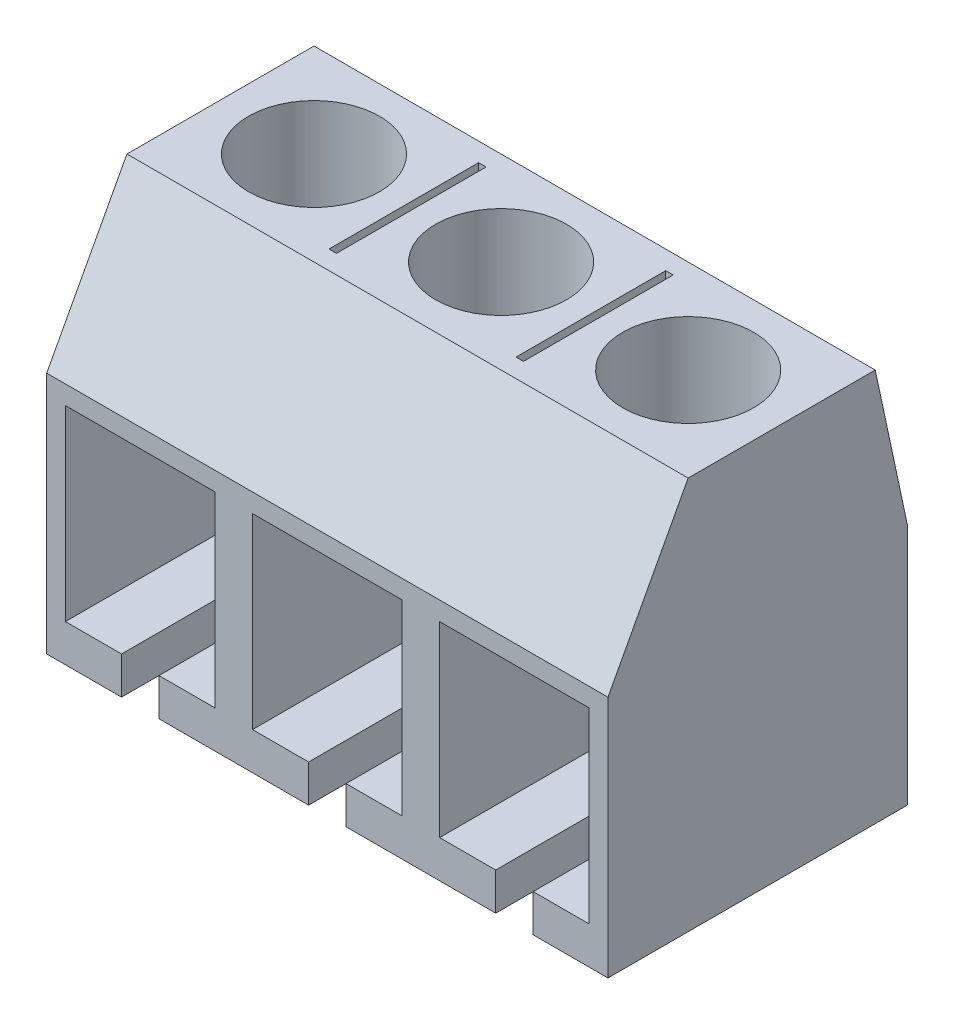
SolidWorks part; units mm, degrees
ref_plane "Ön Düzlem" through (0, 0, 0) normal (0, 0, 1) x (1, 0, 0)
ref_plane "Üst Düzlem" through (0, 0, 0) normal (0, 1, 0) x (1, 0, 0)
ref_plane "Sağ Düzlem" through (0, 0, 0) normal (1, 0, 0) x (0, 0, -1)
sketch "Çizim1" plane through (0, 0, 0) normal (1, 0, 0) x (0, 0, -1)
  line L0 (-4, 1) -> (4, 1) construction
  line L1 (-1.8562, 5) -> (3.1438, 5)
  line L2 (-4, 1) -> (-4, -5.5)
  line L3 (-4, -5.5) -> (4, -5.5)
  line L4 (4, 1) -> (4, -5.5)
  line L5 (-2.6115, 3.5908) -> (4, -5.5) construction
  line L6 (-4, -5.5) -> (3.2558, 4.4767) construction
  line L7 (-4, 1) -> (-1.8562, 5)
  line L8 (4, 1) -> (3.1438, 5)
  point P0 (0, 0)
  dimension "D1" = 10.5
  dimension "D2" = 8
  dimension "D3" = 4
  dimension "D4" = 5
extrude "Yükseklik-Ekstrüzyon1" add sketch "Çizim1" along normal blind 7.5 and the other way blind 7.5
sketch "Çizim2" plane through (0, 0, -4) normal (0, 0, -1) x (-1, 0, 0)
  line L0 (0, 1) -> (0, -5.5) construction
  line L1 (7.5, 1) -> (-7.5, 1) construction
  line L2 (7.5, -5.5) -> (-7.5, -5.5) construction
  line L3 (-0.5, -4.5) -> (-0.5, -5.5)
  line L4 (-2, 0.5) -> (2, 0.5)
  line L5 (-2, 0.5) -> (-2, -4.5)
  line L6 (-2, -4.5) -> (-0.5, -4.5)
  line L7 (2, 0.5) -> (2, -4.5)
  line L8 (-2, 0.5) -> (2, -4.5) construction
  line L9 (-2, -4.5) -> (2, 0.5) construction
  line L10 (0.5, -4.5) -> (0.5, -5.5)
  line L11 (-0.5, -5.5) -> (0.5, -5.5)
  line L12 (0.5, -4.5) -> (2, -4.5)
  line L13 (5, 1) -> (5, -5.5) construction
  line L14 (-5, 1) -> (-5, -5.5) construction
  line L15 (3, 0.5) -> (3, -4.5)
  line L16 (3, -4.5) -> (4.5, -4.5)
  line L17 (4.5, -4.5) -> (4.5, -5.5)
  line L18 (4.5, -5.5) -> (5.5, -5.5)
  line L19 (5.5, -4.5) -> (5.5, -5.5)
  line L20 (5.5, -4.5) -> (7, -4.5)
  line L21 (7, 0.5) -> (7, -4.5)
  line L22 (3, 0.5) -> (7, 0.5)
  line L23 (-7, 0.5) -> (-7, -4.5)
  line L24 (-7, -4.5) -> (-5.5, -4.5)
  line L25 (-5.5, -4.5) -> (-5.5, -5.5)
  line L26 (-5.5, -5.5) -> (-4.5, -5.5)
  line L27 (-4.5, -4.5) -> (-4.5, -5.5)
  line L28 (-4.5, -4.5) -> (-3, -4.5)
  line L29 (-3, 0.5) -> (-3, -4.5)
  line L30 (-7, 0.5) -> (-3, 0.5)
  point P6 (0, -2)
  dimension "D1" = 1
  dimension "D2" = 5
  dimension "D3" = 4
  dimension "D4" = 0.5
  dimension "D5" = 3
  dimension "D6" = 3
  dimension "D7" = 2
  dimension "D8" = 2
extrude "Kes-Ekstrüzyon1" cut sketch "Çizim2" along direction (0, 0, 1) on the side against the normal through all
sketch "Çizim3" plane through (0, 5, 0) normal (0, 1, 0) x (1, 0, 0)
  line L0 (-7.5, 0.6438) -> (7.5, 0.6438) construction
  line L1 (-7.5, 3.1438) -> (-7.5, -1.8562) construction
  line L2 (7.5, 3.1438) -> (7.5, -1.8562) construction
  circle A0 centre (0, 0.6438) radius 1.75
  circle A1 centre (-5, 0.6438) radius 1.75
  circle A2 centre (5, 0.6438) radius 1.75
  dimension "D1" = 3.5
  dimension "D2" = 3.5
  dimension "D3" = 3.5
  dimension "D4" = 2.5
  dimension "D5" = 2.5
extrude "Kes-Ekstrüzyon2" cut sketch "Çizim3" against normal blind 7.5
sketch "Çizim4" plane through (0, 5, 0) normal (0, 1, 0) x (1, 0, 0)
  line L0 (-2.5, 3.1438) -> (-2.5, -1.8562) construction
  line L1 (-7.5, 3.1438) -> (7.5, 3.1438) construction
  line L2 (-7.5, -1.8562) -> (7.5, -1.8562) construction
  line L3 (2.5, 3.1438) -> (2.5, -1.8562) construction
  line L4 (-7.5, 3.1438) -> (-7.5, -1.8562) construction
  line L6 (0, 3.1438) -> (0, -1.8562) construction
  line L7 (-2.6, 2.6438) -> (-2.4, 2.6438)
  line L8 (-2.6, 2.6438) -> (-2.6, -1.3562)
  line L9 (-2.6, -1.3562) -> (-2.4, -1.3562)
  line L10 (-2.4, 2.6438) -> (-2.4, -1.3562)
  line L11 (-2.6, 2.6438) -> (-2.4, -1.3562) construction
  line L12 (-2.6, -1.3562) -> (-2.4, 2.6438) construction
  line L13 (2.6, 2.6438) -> (2.4, 2.6438)
  line L14 (2.4, 2.6438) -> (2.4, -1.3562)
  line L15 (2.6, -1.3562) -> (2.4, -1.3562)
  line L16 (2.6, 2.6438) -> (2.6, -1.3562)
  point P12 (-2.5, 0.6438)
  dimension "D1" = 5
  dimension "D2" = 5
  dimension "D3" = 4
  dimension "D4" = 0.2
extrude "Kes-Ekstrüzyon3" cut sketch "Çizim4" against normal blind 0.2
